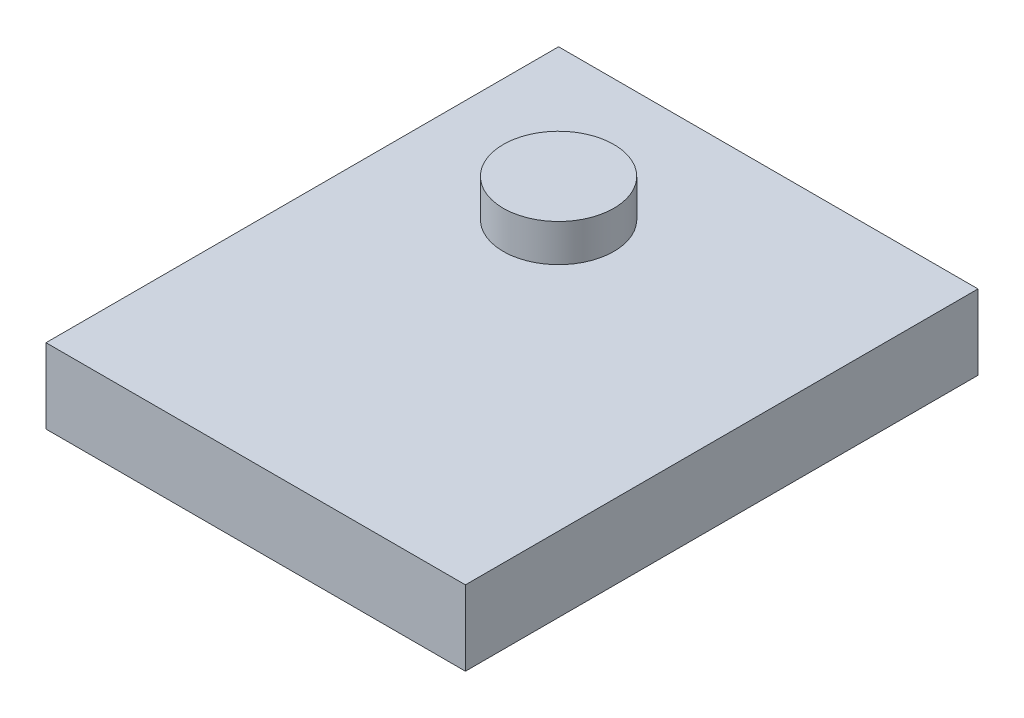
SolidWorks part; units mm, degrees
ref_plane "Front Plane" through (0, 0, 0) normal (0, 0, 1) x (1, 0, 0)
ref_plane "Top Plane" through (0, 0, 0) normal (0, 1, 0) x (1, 0, 0)
ref_plane "Right Plane" through (0, 0, 0) normal (1, 0, 0) x (0, 0, -1)
sketch "Sketch1" plane through (0, 0, 0) normal (0, 1, 0) x (1, 0, 0)
  line L0 (0, 0) -> (30.052, -30.052) construction
  line L1 (0, -42.5) -> (0, 0) construction
  line L3 (-20, 20) -> (36.052, 20)
  line L4 (-20, 20) -> (-20, -48.5)
  line L5 (-20, -48.5) -> (36.052, -48.5)
  line L6 (36.052, 20) -> (36.052, -48.5)
  circle A0 centre (0, 0) radius 7.39
  circle A1 centre (0, -42.5) radius 1.5
  circle A2 centre (30.052, -30.052) radius 1.5
  dimension "D3" = 3
  dimension "D4" = 3
  dimension "D5" = 14.78
  dimension "D1" = 42.5
  dimension "D2" = 42.5
  dimension "D6" = 45
  dimension "D7" = 6
  dimension "D8" = 6
  dimension "D9" = 20
  dimension "D10" = 20
extrude "Boss-Extrude1" add sketch "Sketch1" against normal blind 10 contours A0 | L6 L3 L4 L5 A2 A1 A0 | A2 | A1 region at (8.3758, 0, 14.8339) region at (0, 0, 0) region at (0, 0, 42.5) region at (30.052, 0, 30.052)
extrude "Boss-Extrude2" add sketch "Sketch1<3>" along normal blind 5 contours A0 region at (0, 0, 0)
sketch "Sketch1<3>" plane through (0, 0, 0) normal (0, 1, 0) x (1, 0, 0) same geometry as "Sketch1"
